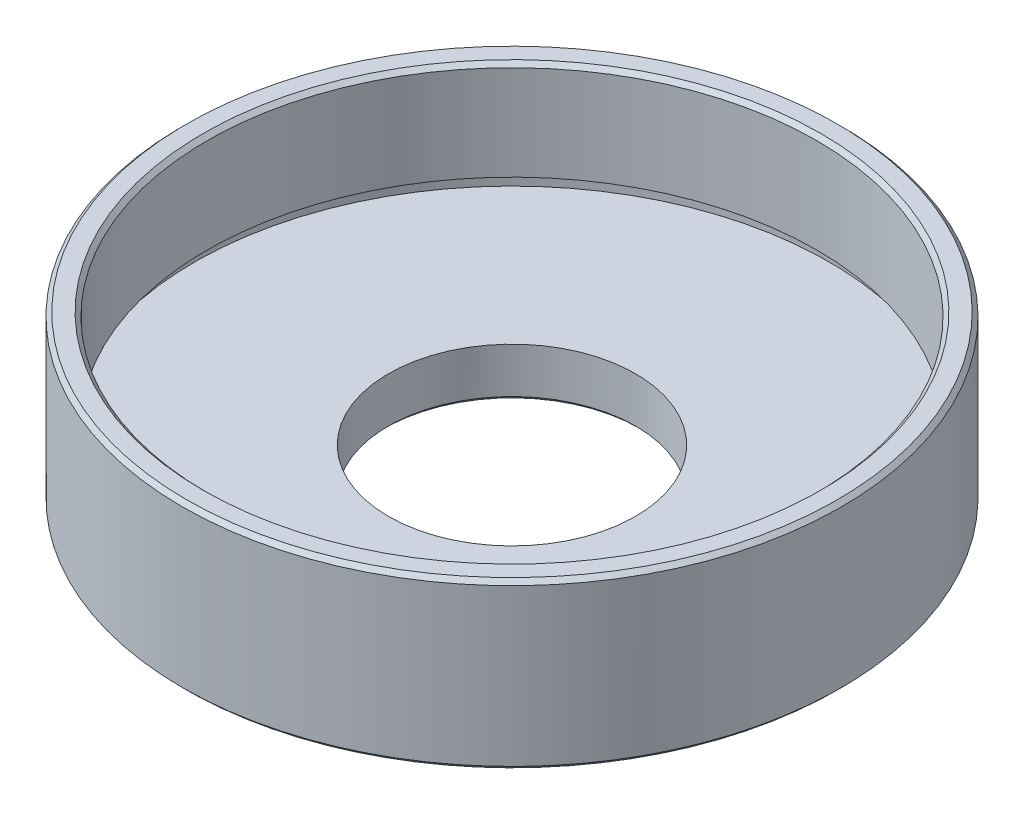
SolidWorks part; units mm, degrees
material "AISI 304"
ref_plane "Спереди" through (0, 0, 0) normal (0, 0, 1) x (1, 0, 0)
ref_plane "Сверху" through (0, 0, 0) normal (0, 1, 0) x (1, 0, 0)
ref_plane "Справа" through (0, 0, 0) normal (1, 0, 0) x (0, 0, -1)
ref_axis "ОсьX" through (-88.99, 0, 0) along (1, 0, 0)
ref_axis "ОсьZ" through (0, 55, 0) along (0, -1, 0)
ref_axis "ОсьY" through (0, 0, -88.99) along (0, 0, 1)
sketch "Эскиз1" plane through (0, 0, 0) normal (0, 0, 1) x (1, 0, 0)
  line L0 (-40, 20) -> (-40, 0)
  line L1 (0, 26.169) -> (0, -22.1581) construction
  line L2 (-40, 0) -> (-15, 0)
  line L3 (-15, 0) -> (-15, 6)
  line L4 (-15, 6) -> (-38.5, 6)
  line L6 (-38.5, 8) -> (-37, 8)
  line L7 (-37, 8) -> (-37, 20)
  line L8 (-37, 20) -> (-40, 20)
  line L11 (-38.5, 8) -> (-38.5, 6)
  dimension "D1" = 80
  dimension "D2" = 20
  dimension "D3" = 74
  dimension "D4" = 30
  dimension "D5" = 6
  dimension "D6" = 1.5
  dimension "D9" = 12
revolve "Повернуть1" add sketch "Эскиз1" angle 360 mid plane about L1
cosmetic thread "Условное изображение резьбы1" parameters "D2"=76
chamfer "Фаска1" distance 0.5 angle 45 4 edges at (0, 0, 15) (0, 0, 40) (0, 20, 40) (0, 20, 37)
